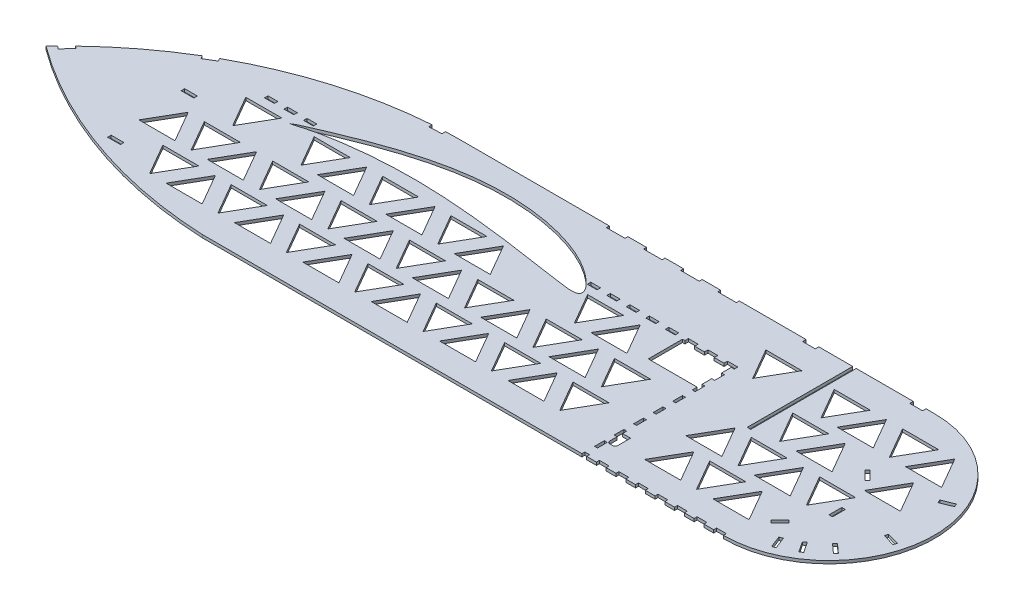
SolidWorks part; units mm, degrees
ref_plane "Front Plane" through (0, 0, 0) normal (0, 0, 1) x (1, 0, 0)
ref_plane "Top Plane" through (0, 0, 0) normal (0, 1, 0) x (1, 0, 0)
ref_plane "Right Plane" through (0, 0, 0) normal (1, 0, 0) x (0, 0, -1)
sketch "Sketch1" plane through (0, 0, 0) normal (0, 1, 0) x (1, 0, 0)
  line L0 (800, 108) -> (0, 108) construction
  line L1 (266.4083, 0) -> (800, 0)
  line L2 (0, 0) -> (0, 216) construction
  line L3 (316.2946, 216) -> (800, 216)
  arc A0 (800, 216) -> (800, 0) centre (800, 108) cw
  arc A2 (266.4083, 0) -> (19.4291, 86.8932) centre (286.1808, 450.645) cw
  arc A4 (19.4291, 86.8932) -> (316.2946, 216) centre (316.2946, -189.8565) cw
  dimension "D1" = 800
  dimension "D2" = 216
extrude "Boss-Extrude1" add sketch "Sketch1" along normal blind 3
sketch "Sketch2" plane through (0, 0, 0) normal (0, -1, 0) x (1, 0, 0)
  line L0 (605.07, -153) -> (605.07, 81) construction
  line L1 (647.57, -153) -> (637.57, -153)
  line L2 (655.07, -153) -> (655.07, -143)
  line L3 (655.07, -118) -> (605.07, -118)
  line L4 (823.6893, -121.2328) -> (814.4969, -130.4252)
  line L5 (814.4969, -130.4252) -> (817.0425, -132.9707)
  line L6 (817.0425, -132.9707) -> (826.2349, -123.7784)
  line L7 (826.2349, -123.7784) -> (823.6893, -121.2328)
  line L8 (823.6893, -121.2328) -> (814.4969, -130.4252)
  line L9 (814.4969, -130.4252) -> (817.0425, -132.9707)
  line L10 (817.0425, -132.9707) -> (826.2349, -123.7784)
  line L11 (826.2349, -123.7784) -> (823.6893, -121.2328)
  line L12 (605.07, -153) -> (605.07, -118)
  line L13 (778.5, -216) -> (791.5, -216) construction
  line L14 (791.5, -216) -> (791.5, -212.4) construction
  line L15 (791.5, -212.4) -> (778.5, -212.4) construction
  line L16 (778.5, -212.4) -> (778.5, -216) construction
  line L17 (668.6076, -216) -> (681.6076, -216) construction
  line L18 (681.6076, -216) -> (681.6076, -212.4) construction
  line L19 (681.6076, -212.4) -> (668.6076, -212.4) construction
  line L20 (833.2163, -28.1278) -> (837.9573, -16.0231)
  line L21 (837.9573, -16.0231) -> (834.6052, -14.7102)
  line L22 (834.6052, -14.7102) -> (829.8642, -26.8149)
  line L23 (829.8642, -26.8149) -> (833.2163, -28.1278)
  line L24 (833.2163, -28.1278) -> (837.9573, -16.0231)
  line L25 (837.9573, -16.0231) -> (834.6052, -14.7102)
  line L26 (834.6052, -14.7102) -> (829.8642, -26.8149)
  line L27 (829.8642, -26.8149) -> (833.2163, -28.1278)
  line L28 (839.4566, -85.3169) -> (839.4566, -72.3169)
  line L29 (839.4566, -72.3169) -> (835.8566, -72.3169)
  line L30 (835.8566, -72.3169) -> (835.8566, -85.3169)
  line L31 (835.8566, -85.3169) -> (839.4566, -85.3169)
  line L32 (839.4566, -85.3169) -> (839.4566, -72.3169)
  line L33 (839.4566, -72.3169) -> (835.8566, -72.3169)
  line L34 (835.8566, -72.3169) -> (835.8566, -85.3169)
  line L35 (835.8566, -85.3169) -> (839.4566, -85.3169)
  line L36 (668.6076, -212.4) -> (668.6076, -216) construction
  line L39 (600.2018, -213) -> (581.2018, -213) construction
  line L40 (658.07, -25.4734) -> (658.07, -38.6734)
  line L41 (663.77, -22.9734) -> (660.57, -22.9734)
  line L42 (666.27, -38.6734) -> (666.27, -25.4734)
  line L43 (658.07, -38.6734) -> (666.27, -38.6734)
  line L44 (658.07, -25.4734) -> (658.07, -33)
  line L45 (663.77, -22.9734) -> (660.57, -22.9734)
  line L46 (666.27, -38.6734) -> (666.27, -25.4734)
  line L47 (658.07, -38.6734) -> (666.27, -38.6734)
  line L48 (581.2018, -213) -> (581.2018, -216) construction
  line L49 (581.2018, -216) -> (600.2018, -216) construction
  line L50 (600.2018, -216) -> (600.2018, -213) construction
  line L51 (562.2018, -213) -> (543.2018, -213) construction
  line L52 (543.2018, -213) -> (543.2018, -216) construction
  line L53 (543.2018, -216) -> (562.2018, -216) construction
  line L54 (562.2018, -216) -> (562.2018, -213) construction
  line L55 (524.2018, -213) -> (505.2018, -213) construction
  line L56 (505.2018, -213) -> (505.2018, -216) construction
  line L57 (505.2018, -216) -> (524.2018, -216) construction
  line L58 (524.2018, -216) -> (524.2018, -213) construction
  line L59 (486.2018, -213) -> (467.2018, -213) construction
  line L60 (467.2018, -213) -> (467.2018, -216) construction
  line L61 (467.2018, -216) -> (486.2018, -216) construction
  line L62 (486.2018, -216) -> (486.2018, -213) construction
  line L63 (286.6536, -215.0679) -> (299.64, -215.6627) construction
  line L64 (299.64, -215.6627) -> (299.8047, -212.0664) construction
  line L65 (299.8047, -212.0664) -> (286.8183, -211.4717) construction
  line L66 (286.8183, -211.4717) -> (286.6536, -215.0679) construction
  line L67 (107.8918, -158.4076) -> (119.0512, -165.0761) construction
  line L68 (119.0512, -165.0761) -> (120.8979, -161.9858) construction
  line L69 (120.8979, -161.9858) -> (109.7385, -155.3173) construction
  line L70 (109.7385, -155.3173) -> (107.8918, -158.4076) construction
  line L71 (25.2251, -93.1105) -> (34.0897, -102.6194) construction
  line L72 (34.0897, -102.6194) -> (36.7229, -100.1646) construction
  line L73 (36.7229, -100.1646) -> (27.8584, -90.6557) construction
  line L74 (27.8584, -90.6557) -> (25.2251, -93.1105) construction
  line L76 (141.0425, -116.6591) -> (128.0425, -116.6591) construction
  line L77 (128.0425, -116.6591) -> (128.0425, -120.2591) construction
  line L79 (212.57, -142.8618) -> (212.57, -142.8948)
  line L80 (128.0425, -120.2591) -> (141.0425, -120.2591) construction
  line L81 (141.0425, -120.2591) -> (141.0425, -116.6591) construction
  line L82 (144.694, -37.8042) -> (131.694, -37.8042) construction
  line L83 (131.694, -37.8042) -> (131.694, -41.4042) construction
  line L84 (131.694, -41.4042) -> (144.694, -41.4042) construction
  line L85 (144.694, -41.4042) -> (144.694, -37.8042) construction
  line L99 (141.0425, -116.6591) -> (128.0425, -116.6591)
  line L101 (128.0425, -116.6591) -> (128.0425, -120.2591)
  line L102 (128.0425, -120.2591) -> (141.0425, -120.2591)
  line L104 (141.0425, -120.2591) -> (141.0425, -116.6591)
  line L105 (144.694, -37.8042) -> (131.694, -37.8042)
  line L106 (131.694, -37.8042) -> (131.694, -41.4042)
  line L108 (131.694, -41.4042) -> (144.694, -41.4042)
  line L110 (144.694, -41.4042) -> (144.694, -37.8042)
  line L111 (237.2859, -101.1604) -> (274.2268, -101.1604)
  line L131 (537.57, -153) -> (527.57, -153) construction
  line L132 (527.57, -153) -> (527.57, -156.6) construction
  line L133 (527.57, -156.6) -> (537.57, -156.6) construction
  line L134 (537.57, -156.6) -> (537.57, -153) construction
  line L135 (557.57, -153) -> (547.57, -153) construction
  line L136 (547.57, -153) -> (547.57, -156.6) construction
  line L137 (547.57, -156.6) -> (557.57, -156.6) construction
  line L138 (557.57, -156.6) -> (557.57, -153) construction
  line L139 (577.57, -153) -> (567.57, -153) construction
  line L140 (567.57, -153) -> (567.57, -156.6) construction
  line L141 (567.57, -156.6) -> (577.57, -156.6) construction
  line L142 (577.57, -156.6) -> (577.57, -153) construction
  line L143 (597.57, -153) -> (587.57, -153) construction
  line L144 (587.57, -153) -> (587.57, -156.6) construction
  line L145 (587.57, -156.6) -> (597.57, -156.6) construction
  line L146 (597.57, -156.6) -> (597.57, -153) construction
  line L148 (607.57, -153) -> (607.57, -156.6) construction
  line L149 (607.57, -156.6) -> (617.57, -156.6) construction
  line L150 (617.57, -156.6) -> (617.57, -153) construction
  line L152 (627.57, -153) -> (627.57, -156.6) construction
  line L153 (627.57, -156.6) -> (637.57, -156.6) construction
  line L154 (637.57, -156.6) -> (637.57, -153) construction
  line L155 (658.07, -153) -> (647.57, -153) construction
  line L156 (647.57, -153) -> (647.57, -156.6) construction
  line L157 (647.57, -156.6) -> (658.07, -156.6) construction
  line L158 (658.07, -156.6) -> (658.07, -153) construction
  line L160 (655.07, -143) -> (658.07, -143) construction
  line L161 (658.07, -143) -> (658.07, -133) construction
  line L162 (658.07, -133) -> (655.07, -133) construction
  line L163 (655.07, -113) -> (655.07, -123) construction
  line L164 (655.07, -123) -> (658.07, -123) construction
  line L165 (658.07, -123) -> (658.07, -113) construction
  line L166 (658.07, -113) -> (655.07, -113) construction
  line L167 (655.07, -93) -> (655.07, -103) construction
  line L168 (655.07, -103) -> (658.07, -103) construction
  line L169 (658.07, -103) -> (658.07, -93) construction
  line L170 (658.07, -93) -> (655.07, -93) construction
  line L171 (655.07, -73) -> (655.07, -83) construction
  line L172 (655.07, -83) -> (658.07, -83) construction
  line L173 (658.07, -83) -> (658.07, -73) construction
  line L174 (658.07, -73) -> (655.07, -73) construction
  line L175 (655.07, -53) -> (655.07, -63) construction
  line L176 (655.07, -63) -> (658.07, -63) construction
  line L177 (658.07, -63) -> (658.07, -53) construction
  line L178 (658.07, -53) -> (655.07, -53) construction
  line L179 (655.07, -33) -> (655.07, -43) construction
  line L180 (655.07, -43) -> (658.07, -43) construction
  line L182 (658.07, -33) -> (655.07, -33) construction
  line L183 (655.07, -13) -> (655.07, -23) construction
  line L184 (655.07, -23) -> (658.07, -23) construction
  line L185 (658.07, -23) -> (658.07, -13) construction
  line L186 (658.07, -13) -> (655.07, -13) construction
  line L187 (660, 0) -> (655.07, 0) construction
  line L188 (879.4661, -142.1765) -> (891.5128, -147.063) construction
  line L189 (891.5128, -147.063) -> (892.866, -143.727) construction
  line L190 (892.866, -143.727) -> (880.8193, -138.8405) construction
  line L191 (880.8193, -138.8405) -> (879.4661, -142.1765) construction
  line L192 (883.5641, -85.6407) -> (896.0497, -82.0199) construction
  line L193 (896.0497, -82.0199) -> (895.047, -78.5624) construction
  line L194 (895.047, -78.5624) -> (882.5614, -82.1832) construction
  line L195 (882.5614, -82.1832) -> (883.5641, -85.6407) construction
  line L196 (865.4007, -51.3816) -> (875.0501, -42.6702) construction
  line L197 (875.0501, -42.6702) -> (872.6378, -39.9981) construction
  line L198 (872.6378, -39.9981) -> (862.9883, -48.7095) construction
  line L199 (862.9883, -48.7095) -> (865.4007, -51.3816) construction
  line L200 (849.1147, -36.7915) -> (856.2715, -25.9389) construction
  line L201 (856.2715, -25.9389) -> (853.2661, -23.957) construction
  line L202 (853.2661, -23.957) -> (846.1093, -34.8096) construction
  line L203 (846.1093, -34.8096) -> (849.1147, -36.7915) construction
  line L204 (822.4089, -44.7346) -> (813.2165, -35.5422) construction
  line L205 (813.2165, -35.5422) -> (810.6709, -38.0878) construction
  line L206 (810.6709, -38.0878) -> (819.8633, -47.2801) construction
  line L207 (819.8633, -47.2801) -> (822.4089, -44.7346) construction
  line L208 (879.4661, -142.1765) -> (891.5128, -147.063)
  line L209 (891.5128, -147.063) -> (892.866, -143.727)
  line L210 (892.866, -143.727) -> (880.8193, -138.8405)
  line L211 (880.8193, -138.8405) -> (879.4661, -142.1765)
  line L212 (883.5641, -85.6407) -> (896.0497, -82.0199)
  line L213 (896.0497, -82.0199) -> (895.047, -78.5624)
  line L214 (895.047, -78.5624) -> (882.5614, -82.1832)
  line L215 (882.5614, -82.1832) -> (883.5641, -85.6407)
  line L216 (865.4007, -51.3816) -> (875.0501, -42.6702)
  line L217 (875.0501, -42.6702) -> (872.6378, -39.9981)
  line L218 (872.6378, -39.9981) -> (862.9883, -48.7095)
  line L219 (862.9883, -48.7095) -> (865.4007, -51.3816)
  line L220 (849.1147, -36.7915) -> (856.2715, -25.9389)
  line L221 (856.2715, -25.9389) -> (853.2661, -23.957)
  line L222 (853.2661, -23.957) -> (846.1093, -34.8096)
  line L223 (846.1093, -34.8096) -> (849.1147, -36.7915)
  line L224 (822.4089, -44.7346) -> (813.2165, -35.5422)
  line L225 (813.2165, -35.5422) -> (810.6709, -38.0878)
  line L226 (810.6709, -38.0878) -> (819.8633, -47.2801)
  line L227 (819.8633, -47.2801) -> (822.4089, -44.7346)
  line L228 (655.07, 0) -> (655.07, -3) construction
  line L229 (655.07, -3) -> (660, -3) construction
  line L230 (660, -3) -> (660, 0) construction
  line L231 (680, 0) -> (670, 0) construction
  line L232 (670, 0) -> (670, -3) construction
  line L233 (670, -3) -> (680, -3) construction
  line L234 (680, -3) -> (680, 0) construction
  line L235 (700, 0) -> (690, 0) construction
  line L236 (690, 0) -> (690, -3) construction
  line L237 (690, -3) -> (700, -3) construction
  line L238 (700, -3) -> (700, 0) construction
  line L239 (720, 0) -> (710, 0) construction
  line L240 (710, 0) -> (710, -3) construction
  line L241 (710, -3) -> (720, -3) construction
  line L242 (720, -3) -> (720, 0) construction
  line L243 (740, 0) -> (730, 0) construction
  line L244 (730, 0) -> (730, -3) construction
  line L245 (730, -3) -> (740, -3) construction
  line L246 (740, -3) -> (740, 0) construction
  line L247 (760, 0) -> (750, 0) construction
  line L248 (750, 0) -> (750, -3) construction
  line L249 (750, -3) -> (760, -3) construction
  line L250 (760, -3) -> (760, 0) construction
  line L251 (780, 0) -> (770, 0) construction
  line L252 (770, 0) -> (770, -3) construction
  line L253 (770, -3) -> (780, -3) construction
  line L254 (780, -3) -> (780, 0) construction
  line L255 (800, 0) -> (790, 0) construction
  line L256 (790, 0) -> (790, -3) construction
  line L257 (790, -3) -> (800, -3) construction
  line L258 (800, -3) -> (800, 0) construction
  line L259 (778.5, -216) -> (791.5, -216)
  line L260 (791.5, -216) -> (791.5, -212.4)
  line L261 (791.5, -212.4) -> (778.5, -212.4)
  line L262 (778.5, -212.4) -> (778.5, -216)
  line L263 (668.6076, -216) -> (681.6076, -216)
  line L264 (681.6076, -216) -> (681.6076, -212.4)
  line L265 (681.6076, -212.4) -> (668.6076, -212.4)
  line L266 (668.6076, -212.4) -> (668.6076, -216)
  line L267 (600.2018, -213) -> (581.2018, -213)
  line L268 (581.2018, -213) -> (581.2018, -216)
  line L269 (581.2018, -216) -> (600.2018, -216)
  line L270 (600.2018, -216) -> (600.2018, -213)
  line L271 (562.2018, -213) -> (543.2018, -213)
  line L272 (543.2018, -213) -> (543.2018, -216)
  line L273 (543.2018, -216) -> (562.2018, -216)
  line L274 (562.2018, -216) -> (562.2018, -213)
  line L275 (524.2018, -213) -> (505.2018, -213)
  line L276 (505.2018, -213) -> (505.2018, -216)
  line L277 (505.2018, -216) -> (524.2018, -216)
  line L278 (524.2018, -216) -> (524.2018, -213)
  line L279 (486.2018, -213) -> (467.2018, -213)
  line L280 (467.2018, -213) -> (467.2018, -216)
  line L281 (467.2018, -216) -> (486.2018, -216)
  line L282 (486.2018, -216) -> (486.2018, -213)
  line L283 (286.6536, -215.0679) -> (299.64, -215.6627)
  line L284 (299.64, -215.6627) -> (299.8047, -212.0664)
  line L285 (299.8047, -212.0664) -> (286.8183, -211.4717)
  line L286 (286.8183, -211.4717) -> (286.6536, -215.0679)
  line L287 (107.8918, -158.4076) -> (119.0512, -165.0761)
  line L288 (119.0512, -165.0761) -> (120.8979, -161.9858)
  line L289 (120.8979, -161.9858) -> (109.7385, -155.3173)
  line L290 (109.7385, -155.3173) -> (107.8918, -158.4076)
  line L291 (25.2251, -93.1105) -> (34.0897, -102.6194)
  line L292 (34.0897, -102.6194) -> (36.7229, -100.1646)
  line L293 (36.7229, -100.1646) -> (27.8584, -90.6557)
  line L294 (27.8584, -90.6557) -> (25.2251, -93.1105)
  line L351 (537.57, -153) -> (527.57, -153)
  line L352 (527.57, -153) -> (527.57, -156.6)
  line L353 (527.57, -156.6) -> (537.57, -156.6)
  line L354 (537.57, -156.6) -> (537.57, -153)
  line L355 (557.57, -153) -> (547.57, -153)
  line L356 (547.57, -153) -> (547.57, -156.6)
  line L357 (547.57, -156.6) -> (557.57, -156.6)
  line L358 (557.57, -156.6) -> (557.57, -153)
  line L359 (577.57, -153) -> (567.57, -153)
  line L360 (567.57, -153) -> (567.57, -156.6)
  line L361 (567.57, -156.6) -> (577.57, -156.6)
  line L362 (577.57, -156.6) -> (577.57, -153)
  line L363 (597.57, -153) -> (587.57, -153)
  line L364 (587.57, -153) -> (587.57, -156.6)
  line L365 (587.57, -156.6) -> (597.57, -156.6)
  line L366 (597.57, -156.6) -> (597.57, -153)
  line L368 (607.57, -153) -> (607.57, -156.6)
  line L369 (607.57, -156.6) -> (617.57, -156.6)
  line L370 (617.57, -156.6) -> (617.57, -153)
  line L372 (627.57, -153) -> (627.57, -156.6)
  line L373 (627.57, -156.6) -> (637.57, -156.6)
  line L374 (637.57, -156.6) -> (637.57, -153)
  line L375 (658.07, -153) -> (655.07, -153)
  line L376 (647.57, -153) -> (647.57, -156.6)
  line L377 (647.57, -156.6) -> (658.07, -156.6)
  line L378 (658.07, -156.6) -> (658.07, -153)
  line L380 (655.07, -143) -> (658.07, -143)
  line L381 (658.07, -143) -> (658.07, -133)
  line L382 (658.07, -133) -> (655.07, -133)
  line L383 (655.07, -113) -> (655.07, -118)
  line L384 (655.07, -123) -> (658.07, -123)
  line L385 (658.07, -123) -> (658.07, -113)
  line L386 (658.07, -113) -> (655.07, -113)
  line L387 (655.07, -93) -> (655.07, -103)
  line L388 (655.07, -103) -> (658.07, -103)
  line L389 (658.07, -103) -> (658.07, -93)
  line L390 (658.07, -93) -> (655.07, -93)
  line L391 (655.07, -73) -> (655.07, -83)
  line L392 (655.07, -83) -> (658.07, -83)
  line L393 (658.07, -83) -> (658.07, -73)
  line L394 (658.07, -73) -> (655.07, -73)
  line L395 (655.07, -53) -> (655.07, -63)
  line L396 (655.07, -63) -> (658.07, -63)
  line L397 (658.07, -63) -> (658.07, -53)
  line L398 (658.07, -53) -> (655.07, -53)
  line L399 (655.07, -33) -> (655.07, -43)
  line L400 (655.07, -43) -> (658.07, -43)
  line L401 (658.07, -43) -> (658.07, -38.6734)
  line L402 (658.07, -33) -> (655.07, -33)
  line L403 (655.07, -13) -> (655.07, -23)
  line L404 (655.07, -23) -> (658.07, -23)
  line L405 (658.07, -23) -> (658.07, -13)
  line L406 (658.07, -13) -> (655.07, -13)
  line L407 (660, 0) -> (655.07, 0)
  line L408 (655.07, 0) -> (655.07, -3)
  line L409 (655.07, -3) -> (660, -3)
  line L410 (660, -3) -> (660, 0)
  line L411 (680, 0) -> (670, 0)
  line L412 (670, 0) -> (670, -3)
  line L413 (670, -3) -> (680, -3)
  line L414 (680, -3) -> (680, 0)
  line L415 (700, 0) -> (690, 0)
  line L416 (690, 0) -> (690, -3)
  line L417 (690, -3) -> (700, -3)
  line L418 (700, -3) -> (700, 0)
  line L419 (720, 0) -> (710, 0)
  line L420 (710, 0) -> (710, -3)
  line L421 (710, -3) -> (720, -3)
  line L422 (720, -3) -> (720, 0)
  line L423 (740, 0) -> (730, 0)
  line L424 (730, 0) -> (730, -3)
  line L425 (730, -3) -> (740, -3)
  line L426 (740, -3) -> (740, 0)
  line L427 (760, 0) -> (750, 0)
  line L428 (750, 0) -> (750, -3)
  line L429 (750, -3) -> (760, -3)
  line L430 (760, -3) -> (760, 0)
  line L431 (780, 0) -> (770, 0)
  line L432 (770, 0) -> (770, -3)
  line L433 (770, -3) -> (780, -3)
  line L434 (780, -3) -> (780, 0)
  line L435 (800, 0) -> (790, 0)
  line L436 (790, 0) -> (790, -3)
  line L437 (790, -3) -> (800, -3)
  line L438 (800, -3) -> (800, 0)
  line L439 (655.07, -133) -> (655.07, -123)
  line L440 (627.57, -153) -> (617.57, -153)
  line L441 (607.57, -153) -> (605.07, -153)
  line L443 (274.2268, -101.1604) -> (255.7563, -69.1686)
  line L444 (255.7563, -69.1686) -> (237.2859, -101.1604)
  line L445 (202.2859, -69.1686) -> (239.2268, -69.1686)
  line L449 (239.2268, -69.1686) -> (220.7563, -101.1604)
  line L450 (220.7563, -101.1604) -> (202.2859, -69.1686)
  line L451 (220.7563, -101.1604) -> (202.2859, -69.1686) construction
  line L452 (239.2268, -69.1686) -> (220.7563, -101.1604) construction
  line L453 (202.2859, -69.1686) -> (239.2268, -69.1686) construction
  line L462 (187.07, -153) -> (177.07, -153) construction
  line L463 (177.07, -153) -> (177.07, -156.6) construction
  line L464 (177.07, -156.6) -> (187.07, -156.6) construction
  line L465 (187.07, -156.6) -> (187.07, -153) construction
  line L466 (207.07, -153) -> (197.07, -153) construction
  line L467 (197.07, -153) -> (197.07, -156.6) construction
  line L468 (197.07, -156.6) -> (207.07, -156.6) construction
  line L469 (207.07, -156.6) -> (207.07, -153) construction
  line L470 (227.07, -153) -> (217.07, -153) construction
  line L471 (217.07, -153) -> (217.07, -156.6) construction
  line L472 (217.07, -156.6) -> (227.07, -156.6) construction
  line L473 (227.07, -156.6) -> (227.07, -153) construction
  line L474 (517.57, -153) -> (507.57, -153) construction
  line L475 (507.57, -153) -> (507.57, -156.6) construction
  line L476 (507.57, -156.6) -> (517.57, -156.6) construction
  line L477 (517.57, -156.6) -> (517.57, -153) construction
  line L478 (187.07, -153) -> (177.07, -153)
  line L479 (177.07, -153) -> (177.07, -156.6)
  line L480 (177.07, -156.6) -> (187.07, -156.6)
  line L481 (187.07, -156.6) -> (187.07, -153)
  line L482 (207.07, -153) -> (197.07, -153)
  line L483 (197.07, -153) -> (197.07, -156.6)
  line L484 (197.07, -156.6) -> (207.07, -156.6)
  line L485 (207.07, -156.6) -> (207.07, -153)
  line L486 (227.07, -153) -> (217.07, -153)
  line L487 (217.07, -153) -> (217.07, -156.6)
  line L488 (217.07, -156.6) -> (227.07, -156.6)
  line L489 (227.07, -156.6) -> (227.07, -153)
  line L490 (517.57, -153) -> (507.57, -153)
  line L491 (507.57, -153) -> (507.57, -156.6)
  line L492 (507.57, -156.6) -> (517.57, -156.6)
  line L493 (517.57, -156.6) -> (517.57, -153)
  line L504 (202.2859, -26.9901) -> (239.2268, -26.9901)
  line L514 (239.2268, -26.9901) -> (220.7563, -58.9818)
  line L515 (132.2859, -69.1686) -> (169.2268, -69.1686)
  line L516 (150.7563, -101.1604) -> (132.2859, -69.1686)
  line L517 (169.2268, -69.1686) -> (150.7563, -101.1604)
  line L518 (202.2859, -69.1686) -> (132.2859, -69.1686) construction
  line L519 (150.7563, -101.1604) -> (220.7563, -101.1604) construction
  line L520 (221.2596, -58.9818) -> (202.7892, -26.9901) construction
  line L521 (167.2859, -101.1604) -> (204.2268, -101.1604)
  line L522 (185.7563, -69.1686) -> (167.2859, -101.1604)
  line L523 (204.2268, -101.1604) -> (185.7563, -69.1686)
  line L524 (239.73, -26.9901) -> (221.2596, -58.9818) construction
  line L525 (202.7892, -26.9901) -> (239.73, -26.9901) construction
  line L526 (132.2859, -26.9901) -> (169.2268, -26.9901) construction
  line L527 (150.7563, -58.9818) -> (132.2859, -26.9901) construction
  line L528 (169.2268, -26.9901) -> (150.7563, -58.9818) construction
  line L529 (166.9552, -58.9818) -> (203.896, -58.9818)
  line L530 (185.4256, -26.9901) -> (166.9552, -58.9818)
  line L531 (203.896, -58.9818) -> (185.4256, -26.9901)
  line L532 (220.7563, -58.9818) -> (202.2859, -26.9901)
  line L533 (236.9552, -58.9818) -> (273.896, -58.9818)
  line L534 (716.4, -108) -> (716.4, -216)
  line L535 (716.4, -216) -> (720, -216)
  line L536 (720, -216) -> (720, -108)
  line L537 (720, -108) -> (716.4, -108)
  line L538 (716.4, -108) -> (716.4, -216)
  line L539 (716.4, -216) -> (720, -216)
  line L540 (720, -216) -> (720, -108)
  line L541 (720, -108) -> (716.4, -108)
  line L542 (273.896, -58.9818) -> (255.4256, -26.9901)
  line L543 (255.4256, -26.9901) -> (236.9552, -58.9818)
  line L544 (307.2859, -101.1604) -> (344.2268, -101.1604)
  line L545 (344.2268, -101.1604) -> (325.7563, -69.1686)
  line L546 (325.7563, -69.1686) -> (307.2859, -101.1604)
  line L547 (272.2859, -69.1686) -> (309.2268, -69.1686)
  line L548 (309.2268, -69.1686) -> (290.7563, -101.1604)
  line L549 (290.7563, -101.1604) -> (272.2859, -69.1686)
  line L550 (272.2859, -26.9901) -> (309.2268, -26.9901)
  line L551 (309.2268, -26.9901) -> (290.7563, -58.9818)
  line L552 (290.7563, -58.9818) -> (272.2859, -26.9901)
  line L553 (306.9552, -58.9818) -> (343.896, -58.9818)
  line L554 (343.896, -58.9818) -> (325.4256, -26.9901)
  line L555 (325.4256, -26.9901) -> (306.9552, -58.9818)
  line L556 (377.2859, -101.1604) -> (414.2268, -101.1604)
  line L557 (414.2268, -101.1604) -> (395.7563, -69.1686)
  line L558 (395.7563, -69.1686) -> (377.2859, -101.1604)
  line L559 (342.2859, -69.1686) -> (379.2268, -69.1686)
  line L560 (379.2268, -69.1686) -> (360.7563, -101.1604)
  line L561 (360.7563, -101.1604) -> (342.2859, -69.1686)
  line L562 (342.2859, -26.9901) -> (379.2268, -26.9901)
  line L563 (379.2268, -26.9901) -> (360.7563, -58.9818)
  line L564 (360.7563, -58.9818) -> (342.2859, -26.9901)
  line L565 (376.9552, -58.9818) -> (413.896, -58.9818)
  line L566 (413.896, -58.9818) -> (395.4256, -26.9901)
  line L567 (395.4256, -26.9901) -> (376.9552, -58.9818)
  line L568 (447.2859, -101.1604) -> (484.2268, -101.1604)
  line L569 (484.2268, -101.1604) -> (465.7563, -69.1686)
  line L570 (465.7563, -69.1686) -> (447.2859, -101.1604)
  line L571 (412.2859, -69.1686) -> (449.2268, -69.1686)
  line L572 (449.2268, -69.1686) -> (430.7563, -101.1604)
  line L573 (430.7563, -101.1604) -> (412.2859, -69.1686)
  line L574 (412.2859, -26.9901) -> (449.2268, -26.9901)
  line L575 (449.2268, -26.9901) -> (430.7563, -58.9818)
  line L576 (430.7563, -58.9818) -> (412.2859, -26.9901)
  line L577 (446.9552, -58.9818) -> (483.896, -58.9818)
  line L578 (483.896, -58.9818) -> (465.4256, -26.9901)
  line L579 (465.4256, -26.9901) -> (446.9552, -58.9818)
  line L580 (517.2859, -101.1604) -> (554.2268, -101.1604)
  line L581 (554.2268, -101.1604) -> (535.7563, -69.1686)
  line L582 (535.7563, -69.1686) -> (517.2859, -101.1604)
  line L583 (482.2859, -69.1686) -> (519.2268, -69.1686)
  line L584 (519.2268, -69.1686) -> (500.7563, -101.1604)
  line L585 (500.7563, -101.1604) -> (482.2859, -69.1686)
  line L586 (482.2859, -26.9901) -> (519.2268, -26.9901)
  line L587 (519.2268, -26.9901) -> (500.7563, -58.9818)
  line L588 (500.7563, -58.9818) -> (482.2859, -26.9901)
  line L589 (516.9552, -58.9818) -> (553.896, -58.9818)
  line L590 (553.896, -58.9818) -> (535.4256, -26.9901)
  line L591 (535.4256, -26.9901) -> (516.9552, -58.9818)
  line L592 (587.2859, -101.1604) -> (624.2268, -101.1604)
  line L593 (624.2268, -101.1604) -> (605.7563, -69.1686)
  line L594 (605.7563, -69.1686) -> (587.2859, -101.1604)
  line L595 (552.2859, -69.1686) -> (589.2268, -69.1686)
  line L596 (589.2268, -69.1686) -> (570.7563, -101.1604)
  line L597 (570.7563, -101.1604) -> (552.2859, -69.1686)
  line L598 (552.2859, -26.9901) -> (589.2268, -26.9901)
  line L599 (589.2268, -26.9901) -> (570.7563, -58.9818)
  line L600 (570.7563, -58.9818) -> (552.2859, -26.9901)
  line L601 (586.9552, -58.9818) -> (623.896, -58.9818)
  line L602 (623.896, -58.9818) -> (605.4256, -26.9901)
  line L603 (605.4256, -26.9901) -> (586.9552, -58.9818)
  line L616 (727.2859, -101.1604) -> (764.2268, -101.1604)
  line L617 (764.2268, -101.1604) -> (745.7563, -69.1686)
  line L618 (745.7563, -69.1686) -> (727.2859, -101.1604)
  line L619 (692.2859, -69.1686) -> (729.2268, -69.1686)
  line L620 (729.2268, -69.1686) -> (710.7563, -101.1604)
  line L621 (710.7563, -101.1604) -> (692.2859, -69.1686)
  line L622 (692.2859, -26.9901) -> (729.2268, -26.9901)
  line L623 (729.2268, -26.9901) -> (710.7563, -58.9818)
  line L624 (710.7563, -58.9818) -> (692.2859, -26.9901)
  line L625 (726.9552, -58.9818) -> (763.896, -58.9818)
  line L626 (763.896, -58.9818) -> (745.4256, -26.9901)
  line L627 (745.4256, -26.9901) -> (726.9552, -58.9818)
  line L628 (797.2859, -101.1604) -> (834.2268, -101.1604)
  line L629 (834.2268, -101.1604) -> (815.7563, -69.1686)
  line L630 (815.7563, -69.1686) -> (797.2859, -101.1604)
  line L631 (762.2859, -69.1686) -> (799.2268, -69.1686)
  line L632 (799.2268, -69.1686) -> (780.7563, -101.1604)
  line L633 (780.7563, -101.1604) -> (762.2859, -69.1686)
  line L634 (762.2859, -26.9901) -> (799.2268, -26.9901)
  line L635 (799.2268, -26.9901) -> (780.7563, -58.9818)
  line L636 (780.7563, -58.9818) -> (762.2859, -26.9901)
  line L661 (236.9552, -143.9818) -> (273.896, -143.9818)
  line L662 (273.896, -143.9818) -> (255.4256, -111.9901)
  line L663 (255.4256, -111.9901) -> (236.9552, -143.9818)
  line L670 (272.2859, -111.9901) -> (309.2268, -111.9901)
  line L671 (309.2268, -111.9901) -> (290.7563, -143.9818)
  line L672 (290.7563, -143.9818) -> (272.2859, -111.9901)
  line L673 (306.9552, -143.9818) -> (343.896, -143.9818)
  line L674 (343.896, -143.9818) -> (325.4256, -111.9901)
  line L675 (325.4256, -111.9901) -> (306.9552, -143.9818)
  line L682 (342.2859, -111.9901) -> (379.2268, -111.9901)
  line L683 (379.2268, -111.9901) -> (360.7563, -143.9818)
  line L684 (360.7563, -143.9818) -> (342.2859, -111.9901)
  line L685 (376.9552, -143.9818) -> (413.896, -143.9818)
  line L686 (413.896, -143.9818) -> (395.4256, -111.9901)
  line L687 (395.4256, -111.9901) -> (376.9552, -143.9818)
  line L694 (412.2859, -111.9901) -> (449.2268, -111.9901)
  line L695 (449.2268, -111.9901) -> (430.7563, -143.9818)
  line L696 (430.7563, -143.9818) -> (412.2859, -111.9901)
  line L709 (516.9552, -143.9818) -> (553.896, -143.9818)
  line L710 (553.896, -143.9818) -> (535.4256, -111.9901)
  line L711 (535.4256, -111.9901) -> (516.9552, -143.9818)
  line L718 (552.2859, -111.9901) -> (589.2268, -111.9901)
  line L719 (589.2268, -111.9901) -> (570.7563, -143.9818)
  line L720 (570.7563, -143.9818) -> (552.2859, -111.9901)
  line L724 (657.2859, -186.1604) -> (694.2268, -186.1604)
  line L725 (694.2268, -186.1604) -> (675.7563, -154.1686)
  line L726 (675.7563, -154.1686) -> (657.2859, -186.1604)
  line L736 (727.2859, -186.1604) -> (764.2268, -186.1604)
  line L737 (764.2268, -186.1604) -> (745.7563, -154.1686)
  line L738 (745.7563, -154.1686) -> (727.2859, -186.1604)
  line L745 (726.9552, -143.9818) -> (763.896, -143.9818)
  line L746 (763.896, -143.9818) -> (745.4256, -111.9901)
  line L747 (745.4256, -111.9901) -> (726.9552, -143.9818)
  line L748 (797.2859, -186.1604) -> (834.2268, -186.1604)
  line L749 (834.2268, -186.1604) -> (815.7563, -154.1686)
  line L750 (815.7563, -154.1686) -> (797.2859, -186.1604)
  line L751 (762.2859, -154.1686) -> (799.2268, -154.1686)
  line L752 (799.2268, -154.1686) -> (780.7563, -186.1604)
  line L753 (780.7563, -186.1604) -> (762.2859, -154.1686)
  line L754 (762.2859, -111.9901) -> (799.2268, -111.9901)
  line L755 (799.2268, -111.9901) -> (780.7563, -143.9818)
  line L756 (780.7563, -143.9818) -> (762.2859, -111.9901)
  line L763 (832.2859, -154.1686) -> (869.2268, -154.1686)
  line L764 (869.2268, -154.1686) -> (850.7563, -186.1604)
  line L765 (850.7563, -186.1604) -> (832.2859, -154.1686)
  line L766 (832.2859, -111.9901) -> (869.2268, -111.9901)
  line L767 (869.2268, -111.9901) -> (850.7563, -143.9818)
  line L768 (850.7563, -143.9818) -> (832.2859, -111.9901)
  line L901 (166.9552, -143.9818) -> (203.896, -143.9818)
  line L902 (203.896, -143.9818) -> (185.4256, -111.9901)
  line L903 (185.4256, -111.9901) -> (166.9552, -143.9818)
  line L916 (167.2859, -101.1604) -> (237.2859, -101.1604) construction
  line L917 (167.2859, -101.1604) -> (167.2859, -186.1604) construction
  line L918 (832.2859, -69.1686) -> (869.2268, -69.1686) [skipped]
  line L919 (869.2268, -69.1686) -> (850.7563, -101.1604) [skipped]
  line L920 (850.7563, -101.1604) -> (832.2859, -69.1686) [skipped]
  line L921 (796.9552, -58.9818) -> (833.896, -58.9818) [skipped]
  line L922 (833.896, -58.9818) -> (815.4256, -26.9901) [skipped]
  line L923 (815.4256, -26.9901) -> (796.9552, -58.9818) [skipped]
  line L924 (796.9552, -143.9818) -> (833.896, -143.9818) [skipped]
  line L925 (833.896, -143.9818) -> (815.4256, -111.9901) [skipped]
  line L926 (815.4256, -111.9901) -> (796.9552, -143.9818) [skipped]
  line L927 (866.9552, -58.9818) -> (903.896, -58.9818) [skipped]
  line L928 (903.896, -58.9818) -> (885.4256, -26.9901) [skipped]
  line L929 (885.4256, -26.9901) -> (866.9552, -58.9818) [skipped]
  line L930 (832.2859, -26.9901) -> (869.2268, -26.9901) [skipped]
  line L931 (869.2268, -26.9901) -> (850.7563, -58.9818) [skipped]
  line L932 (850.7563, -58.9818) -> (832.2859, -26.9901) [skipped]
  line L933 (867.2859, -101.1604) -> (904.2268, -101.1604) [skipped]
  line L934 (904.2268, -101.1604) -> (885.7563, -69.1686) [skipped]
  line L935 (885.7563, -69.1686) -> (867.2859, -101.1604) [skipped]
  line L936 (866.9552, -143.9818) -> (903.896, -143.9818) [skipped]
  line L937 (903.896, -143.9818) -> (885.4256, -111.9901) [skipped]
  line L938 (885.4256, -111.9901) -> (866.9552, -143.9818) [skipped]
  line L939 (867.2859, -186.1604) -> (904.2268, -186.1604) [skipped]
  line L940 (904.2268, -186.1604) -> (885.7563, -154.1686) [skipped]
  line L941 (885.7563, -154.1686) -> (867.2859, -186.1604) [skipped]
  line L942 (832.2859, -196.9901) -> (869.2268, -196.9901) [skipped]
  line L943 (869.2268, -196.9901) -> (850.7563, -228.9818) [skipped]
  line L944 (850.7563, -228.9818) -> (832.2859, -196.9901) [skipped]
  line L945 (796.9552, -228.9818) -> (833.896, -228.9818) [skipped]
  line L946 (833.896, -228.9818) -> (815.4256, -196.9901) [skipped]
  line L947 (815.4256, -196.9901) -> (796.9552, -228.9818) [skipped]
  line L948 (866.9552, -228.9818) -> (903.896, -228.9818) [skipped]
  line L949 (903.896, -228.9818) -> (885.4256, -196.9901) [skipped]
  line L950 (885.4256, -196.9901) -> (866.9552, -228.9818) [skipped]
  line L951 (867.2859, -271.1604) -> (904.2268, -271.1604) [skipped]
  line L952 (904.2268, -271.1604) -> (885.7563, -239.1686) [skipped]
  line L953 (885.7563, -239.1686) -> (867.2859, -271.1604) [skipped]
  line L954 (832.2859, -239.1686) -> (869.2268, -239.1686) [skipped]
  line L955 (869.2268, -239.1686) -> (850.7563, -271.1604) [skipped]
  line L956 (850.7563, -271.1604) -> (832.2859, -239.1686) [skipped]
  line L957 (797.2859, -271.1604) -> (834.2268, -271.1604) [skipped]
  line L958 (834.2268, -271.1604) -> (815.7563, -239.1686) [skipped]
  line L959 (815.7563, -239.1686) -> (797.2859, -271.1604) [skipped]
  line L960 (762.2859, -239.1686) -> (799.2268, -239.1686) [skipped]
  line L961 (799.2268, -239.1686) -> (780.7563, -271.1604) [skipped]
  line L962 (780.7563, -271.1604) -> (762.2859, -239.1686) [skipped]
  line L963 (727.2859, -271.1604) -> (764.2268, -271.1604) [skipped]
  line L964 (764.2268, -271.1604) -> (745.7563, -239.1686) [skipped]
  line L965 (745.7563, -239.1686) -> (727.2859, -271.1604) [skipped]
  line L966 (692.2859, -239.1686) -> (729.2268, -239.1686) [skipped]
  line L967 (729.2268, -239.1686) -> (710.7563, -271.1604) [skipped]
  line L968 (710.7563, -271.1604) -> (692.2859, -239.1686) [skipped]
  line L969 (657.2859, -271.1604) -> (694.2268, -271.1604) [skipped]
  line L970 (694.2268, -271.1604) -> (675.7563, -239.1686) [skipped]
  line L971 (675.7563, -239.1686) -> (657.2859, -271.1604) [skipped]
  line L972 (622.2859, -239.1686) -> (659.2268, -239.1686) [skipped]
  line L973 (659.2268, -239.1686) -> (640.7563, -271.1604) [skipped]
  line L974 (640.7563, -271.1604) -> (622.2859, -239.1686) [skipped]
  line L975 (587.2859, -271.1604) -> (624.2268, -271.1604) [skipped]
  line L976 (624.2268, -271.1604) -> (605.7563, -239.1686) [skipped]
  line L977 (605.7563, -239.1686) -> (587.2859, -271.1604) [skipped]
  line L978 (552.2859, -239.1686) -> (589.2268, -239.1686) [skipped]
  line L979 (589.2268, -239.1686) -> (570.7563, -271.1604) [skipped]
  line L980 (570.7563, -271.1604) -> (552.2859, -239.1686) [skipped]
  line L981 (517.2859, -271.1604) -> (554.2268, -271.1604) [skipped]
  line L982 (554.2268, -271.1604) -> (535.7563, -239.1686) [skipped]
  line L983 (535.7563, -239.1686) -> (517.2859, -271.1604) [skipped]
  line L984 (482.2859, -239.1686) -> (519.2268, -239.1686) [skipped]
  line L985 (519.2268, -239.1686) -> (500.7563, -271.1604) [skipped]
  line L986 (500.7563, -271.1604) -> (482.2859, -239.1686) [skipped]
  line L987 (447.2859, -271.1604) -> (484.2268, -271.1604) [skipped]
  line L988 (484.2268, -271.1604) -> (465.7563, -239.1686) [skipped]
  line L989 (465.7563, -239.1686) -> (447.2859, -271.1604) [skipped]
  line L990 (762.2859, -196.9901) -> (799.2268, -196.9901) [skipped]
  line L991 (799.2268, -196.9901) -> (780.7563, -228.9818) [skipped]
  line L992 (780.7563, -228.9818) -> (762.2859, -196.9901) [skipped]
  line L993 (726.9552, -228.9818) -> (763.896, -228.9818) [skipped]
  line L994 (763.896, -228.9818) -> (745.4256, -196.9901) [skipped]
  line L995 (745.4256, -196.9901) -> (726.9552, -228.9818) [skipped]
  line L996 (692.2859, -196.9901) -> (729.2268, -196.9901) [skipped]
  line L997 (729.2268, -196.9901) -> (710.7563, -228.9818) [skipped]
  line L998 (710.7563, -228.9818) -> (692.2859, -196.9901) [skipped]
  line L999 (656.9552, -228.9818) -> (693.896, -228.9818) [skipped]
  line L1000 (693.896, -228.9818) -> (675.4256, -196.9901) [skipped]
  line L1001 (675.4256, -196.9901) -> (656.9552, -228.9818) [skipped]
  line L1002 (622.2859, -196.9901) -> (659.2268, -196.9901) [skipped]
  line L1003 (659.2268, -196.9901) -> (640.7563, -228.9818) [skipped]
  line L1004 (640.7563, -228.9818) -> (622.2859, -196.9901) [skipped]
  line L1005 (586.9552, -228.9818) -> (623.896, -228.9818) [skipped]
  line L1006 (623.896, -228.9818) -> (605.4256, -196.9901) [skipped]
  line L1007 (605.4256, -196.9901) -> (586.9552, -228.9818) [skipped]
  line L1008 (552.2859, -196.9901) -> (589.2268, -196.9901) [skipped]
  line L1009 (589.2268, -196.9901) -> (570.7563, -228.9818) [skipped]
  line L1010 (570.7563, -228.9818) -> (552.2859, -196.9901) [skipped]
  line L1011 (516.9552, -228.9818) -> (553.896, -228.9818) [skipped]
  line L1012 (553.896, -228.9818) -> (535.4256, -196.9901) [skipped]
  line L1013 (535.4256, -196.9901) -> (516.9552, -228.9818) [skipped]
  line L1014 (482.2859, -196.9901) -> (519.2268, -196.9901) [skipped]
  line L1015 (519.2268, -196.9901) -> (500.7563, -228.9818) [skipped]
  line L1016 (500.7563, -228.9818) -> (482.2859, -196.9901) [skipped]
  line L1017 (692.2859, -154.1686) -> (729.2268, -154.1686) [skipped]
  line L1018 (729.2268, -154.1686) -> (710.7563, -186.1604) [skipped]
  line L1019 (710.7563, -186.1604) -> (692.2859, -154.1686) [skipped]
  line L1020 (692.2859, -111.9901) -> (729.2268, -111.9901) [skipped]
  line L1021 (729.2268, -111.9901) -> (710.7563, -143.9818) [skipped]
  line L1022 (710.7563, -143.9818) -> (692.2859, -111.9901) [skipped]
  line L1023 (622.2859, -154.1686) -> (659.2268, -154.1686) [skipped]
  line L1024 (659.2268, -154.1686) -> (640.7563, -186.1604) [skipped]
  line L1025 (640.7563, -186.1604) -> (622.2859, -154.1686) [skipped]
  line L1026 (622.2859, -111.9901) -> (659.2268, -111.9901) [skipped]
  line L1027 (640.7563, -143.9818) -> (622.2859, -111.9901) [skipped]
  line L1028 (659.2268, -111.9901) -> (640.7563, -143.9818) [skipped]
  line L1029 (622.2859, -69.1686) -> (659.2268, -69.1686) [skipped]
  line L1030 (640.7563, -101.1604) -> (622.2859, -69.1686) [skipped]
  line L1031 (659.2268, -69.1686) -> (640.7563, -101.1604) [skipped]
  line L1032 (622.2859, -26.9901) -> (659.2268, -26.9901) [skipped]
  line L1033 (640.7563, -58.9818) -> (622.2859, -26.9901) [skipped]
  line L1034 (659.2268, -26.9901) -> (640.7563, -58.9818) [skipped]
  line L1035 (675.4256, -26.9901) -> (656.9552, -58.9818) [skipped]
  line L1036 (693.896, -58.9818) -> (675.4256, -26.9901) [skipped]
  line L1037 (656.9552, -58.9818) -> (693.896, -58.9818) [skipped]
  line L1038 (675.7563, -69.1686) -> (657.2859, -101.1604) [skipped]
  line L1039 (694.2268, -101.1604) -> (675.7563, -69.1686) [skipped]
  line L1040 (657.2859, -101.1604) -> (694.2268, -101.1604) [skipped]
  line L1041 (675.4256, -111.9901) -> (656.9552, -143.9818) [skipped]
  line L1042 (693.896, -143.9818) -> (675.4256, -111.9901) [skipped]
  line L1043 (656.9552, -143.9818) -> (693.896, -143.9818) [skipped]
  line L1044 (605.4256, -111.9901) -> (586.9552, -143.9818) [skipped]
  line L1045 (623.896, -143.9818) -> (605.4256, -111.9901) [skipped]
  line L1046 (586.9552, -143.9818) -> (623.896, -143.9818) [skipped]
  line L1047 (482.2859, -154.1686) -> (519.2268, -154.1686) [skipped]
  line L1048 (519.2268, -154.1686) -> (500.7563, -186.1604) [skipped]
  line L1049 (500.7563, -186.1604) -> (482.2859, -154.1686) [skipped]
  line L1050 (517.2859, -186.1604) -> (554.2268, -186.1604) [skipped]
  line L1051 (554.2268, -186.1604) -> (535.7563, -154.1686) [skipped]
  line L1052 (535.7563, -154.1686) -> (517.2859, -186.1604) [skipped]
  line L1053 (552.2859, -154.1686) -> (589.2268, -154.1686) [skipped]
  line L1054 (589.2268, -154.1686) -> (570.7563, -186.1604) [skipped]
  line L1055 (570.7563, -186.1604) -> (552.2859, -154.1686) [skipped]
  line L1056 (587.2859, -186.1604) -> (624.2268, -186.1604) [skipped]
  line L1057 (624.2268, -186.1604) -> (605.7563, -154.1686) [skipped]
  line L1058 (605.7563, -154.1686) -> (587.2859, -186.1604) [skipped]
  line L1059 (484.2268, -186.1604) -> (465.7563, -154.1686) [skipped]
  line L1060 (465.7563, -154.1686) -> (447.2859, -186.1604) [skipped]
  line L1061 (447.2859, -186.1604) -> (484.2268, -186.1604) [skipped]
  line L1062 (412.2859, -154.1686) -> (449.2268, -154.1686) [skipped]
  line L1063 (430.7563, -186.1604) -> (412.2859, -154.1686) [skipped]
  line L1064 (449.2268, -154.1686) -> (430.7563, -186.1604) [skipped]
  line L1065 (395.7563, -154.1686) -> (377.2859, -186.1604) [skipped]
  line L1066 (414.2268, -186.1604) -> (395.7563, -154.1686) [skipped]
  line L1067 (377.2859, -186.1604) -> (414.2268, -186.1604) [skipped]
  line L1068 (379.2268, -154.1686) -> (360.7563, -186.1604) [skipped]
  line L1069 (342.2859, -154.1686) -> (379.2268, -154.1686) [skipped]
  line L1070 (360.7563, -186.1604) -> (342.2859, -154.1686) [skipped]
  line L1071 (325.7563, -154.1686) -> (307.2859, -186.1604) [skipped]
  line L1072 (344.2268, -186.1604) -> (325.7563, -154.1686) [skipped]
  line L1073 (307.2859, -186.1604) -> (344.2268, -186.1604) [skipped]
  line L1074 (309.2268, -154.1686) -> (290.7563, -186.1604) [skipped]
  line L1075 (290.7563, -186.1604) -> (272.2859, -154.1686) [skipped]
  line L1076 (272.2859, -154.1686) -> (309.2268, -154.1686) [skipped]
  line L1077 (274.2268, -186.1604) -> (255.7563, -154.1686) [skipped]
  line L1078 (237.2859, -186.1604) -> (274.2268, -186.1604) [skipped]
  line L1079 (255.7563, -154.1686) -> (237.2859, -186.1604) [skipped]
  line L1080 (220.7563, -186.1604) -> (202.2859, -154.1686) [skipped]
  line L1081 (202.2859, -154.1686) -> (239.2268, -154.1686) [skipped]
  line L1082 (239.2268, -154.1686) -> (220.7563, -186.1604) [skipped]
  line L1083 (220.7563, -228.9818) -> (202.2859, -196.9901) [skipped]
  line L1084 (202.2859, -196.9901) -> (239.2268, -196.9901) [skipped]
  line L1085 (239.2268, -196.9901) -> (220.7563, -228.9818) [skipped]
  line L1086 (220.7563, -271.1604) -> (202.2859, -239.1686) [skipped]
  line L1087 (202.2859, -239.1686) -> (239.2268, -239.1686) [skipped]
  line L1088 (239.2268, -239.1686) -> (220.7563, -271.1604) [skipped]
  line L1089 (237.2859, -271.1604) -> (274.2268, -271.1604) [skipped]
  line L1090 (255.7563, -239.1686) -> (237.2859, -271.1604) [skipped]
  line L1091 (274.2268, -271.1604) -> (255.7563, -239.1686) [skipped]
  line L1092 (236.9552, -228.9818) -> (273.896, -228.9818) [skipped]
  line L1093 (273.896, -228.9818) -> (255.4256, -196.9901) [skipped]
  line L1094 (255.4256, -196.9901) -> (236.9552, -228.9818) [skipped]
  line L1095 (290.7563, -228.9818) -> (272.2859, -196.9901) [skipped]
  line L1096 (309.2268, -196.9901) -> (290.7563, -228.9818) [skipped]
  line L1097 (272.2859, -196.9901) -> (309.2268, -196.9901) [skipped]
  line L1098 (325.4256, -196.9901) -> (306.9552, -228.9818) [skipped]
  line L1099 (306.9552, -228.9818) -> (343.896, -228.9818) [skipped]
  line L1100 (343.896, -228.9818) -> (325.4256, -196.9901) [skipped]
  line L1101 (272.2859, -239.1686) -> (309.2268, -239.1686) [skipped]
  line L1102 (309.2268, -239.1686) -> (290.7563, -271.1604) [skipped]
  line L1103 (290.7563, -271.1604) -> (272.2859, -239.1686) [skipped]
  line L1104 (325.7563, -239.1686) -> (307.2859, -271.1604) [skipped]
  line L1105 (307.2859, -271.1604) -> (344.2268, -271.1604) [skipped]
  line L1106 (344.2268, -271.1604) -> (325.7563, -239.1686) [skipped]
  line L1107 (360.7563, -271.1604) -> (342.2859, -239.1686) [skipped]
  line L1108 (379.2268, -239.1686) -> (360.7563, -271.1604) [skipped]
  line L1109 (342.2859, -239.1686) -> (379.2268, -239.1686) [skipped]
  line L1110 (379.2268, -196.9901) -> (360.7563, -228.9818) [skipped]
  line L1111 (360.7563, -228.9818) -> (342.2859, -196.9901) [skipped]
  line L1112 (342.2859, -196.9901) -> (379.2268, -196.9901) [skipped]
  line L1113 (395.4256, -196.9901) -> (376.9552, -228.9818) [skipped]
  line L1114 (376.9552, -228.9818) -> (413.896, -228.9818) [skipped]
  line L1115 (413.896, -228.9818) -> (395.4256, -196.9901) [skipped]
  line L1116 (414.2268, -271.1604) -> (395.7563, -239.1686) [skipped]
  line L1117 (395.7563, -239.1686) -> (377.2859, -271.1604) [skipped]
  line L1118 (377.2859, -271.1604) -> (414.2268, -271.1604) [skipped]
  line L1119 (430.7563, -271.1604) -> (412.2859, -239.1686) [skipped]
  line L1120 (449.2268, -239.1686) -> (430.7563, -271.1604) [skipped]
  line L1121 (412.2859, -239.1686) -> (449.2268, -239.1686) [skipped]
  line L1122 (430.7563, -228.9818) -> (412.2859, -196.9901) [skipped]
  line L1123 (449.2268, -196.9901) -> (430.7563, -228.9818) [skipped]
  line L1124 (412.2859, -196.9901) -> (449.2268, -196.9901) [skipped]
  line L1125 (465.4256, -196.9901) -> (446.9552, -228.9818) [skipped]
  line L1126 (483.896, -228.9818) -> (465.4256, -196.9901) [skipped]
  line L1127 (446.9552, -228.9818) -> (483.896, -228.9818) [skipped]
  line L1128 (166.9552, -228.9818) -> (203.896, -228.9818) [skipped]
  line L1129 (203.896, -228.9818) -> (185.4256, -196.9901) [skipped]
  line L1130 (185.4256, -196.9901) -> (166.9552, -228.9818) [skipped]
  line L1131 (132.2859, -196.9901) -> (169.2268, -196.9901) [skipped]
  line L1132 (169.2268, -196.9901) -> (150.7563, -228.9818) [skipped]
  line L1133 (150.7563, -228.9818) -> (132.2859, -196.9901) [skipped]
  line L1134 (132.2859, -239.1686) -> (169.2268, -239.1686) [skipped]
  line L1135 (169.2268, -239.1686) -> (150.7563, -271.1604) [skipped]
  line L1136 (150.7563, -271.1604) -> (132.2859, -239.1686) [skipped]
  line L1137 (167.2859, -271.1604) -> (204.2268, -271.1604) [skipped]
  line L1138 (204.2268, -271.1604) -> (185.7563, -239.1686) [skipped]
  line L1139 (185.7563, -239.1686) -> (167.2859, -271.1604) [skipped]
  line L1140 (167.2859, -186.1604) -> (204.2268, -186.1604) [skipped]
  line L1141 (204.2268, -186.1604) -> (185.7563, -154.1686) [skipped]
  line L1142 (185.7563, -154.1686) -> (167.2859, -186.1604) [skipped]
  line L1143 (132.2859, -154.1686) -> (169.2268, -154.1686) [skipped]
  line L1144 (169.2268, -154.1686) -> (150.7563, -186.1604) [skipped]
  line L1145 (150.7563, -186.1604) -> (132.2859, -154.1686) [skipped]
  line L1146 (132.2859, -111.9901) -> (169.2268, -111.9901) [skipped]
  line L1147 (169.2268, -111.9901) -> (150.7563, -143.9818) [skipped]
  line L1148 (150.7563, -143.9818) -> (132.2859, -111.9901) [skipped]
  line L1153 (202.2859, -111.9901) -> (239.2268, -111.9901) [skipped]
  line L1154 (239.2268, -111.9901) -> (220.7563, -143.9818) [skipped]
  line L1155 (220.7563, -143.9818) -> (202.2859, -111.9901) [skipped]
  line L1156 (446.9552, -143.9818) -> (483.896, -143.9818) [skipped]
  line L1157 (483.896, -143.9818) -> (465.4256, -111.9901) [skipped]
  line L1158 (465.4256, -111.9901) -> (446.9552, -143.9818) [skipped]
  line L1159 (482.2859, -111.9901) -> (519.2268, -111.9901) [skipped]
  line L1160 (519.2268, -111.9901) -> (500.7563, -143.9818) [skipped]
  line L1161 (500.7563, -143.9818) -> (482.2859, -111.9901) [skipped]
  arc A2 (660.57, -22.9734) -> (658.07, -25.4734) centre (660.57, -25.4734) ccw
  arc A3 (666.27, -25.4734) -> (663.77, -22.9734) centre (663.77, -25.4734) ccw
  arc A4 (660.57, -22.9734) -> (658.07, -25.4734) centre (660.57, -25.4734) ccw
  arc A5 (666.27, -25.4734) -> (663.77, -22.9734) centre (663.77, -25.4734) ccw
  spline S1 degree 3 poles (-1490.7318, -2611.0866) (189.7857, -85.4289) (191.8397, -130.7262) (215.6642, -144.8206) (218.7234, -146.3779) (222.7838, -148.1804) (227.7591, -150.3808) (233.6732, -152.9729) (243.3346, -157.074) (254.0716, -161.5286) (265.8113, -166.1514) (275.5598, -169.7926) (285.8203, -173.3897) (300.2132, -178.0429) (315.0475, -182.2144) (330.2168, -185.6782) (341.7168, -187.8628) (353.2384, -189.5705) (364.7498, -190.7898) (376.2222, -191.4893) (387.6115, -191.6869) (398.8538, -191.3647) (413.4214, -190.2963) (427.5808, -188.3) (441.1954, -185.4275) (450.8219, -182.9197) (459.9489, -180.0697) (468.5117, -176.8876) (476.4536, -173.4247) (483.7151, -169.7289) (490.2481, -165.8848) (496.0197, -162.0069) (500.998, -158.1857) (505.1476, -154.4841) (508.4473, -150.9827) (510.8522, -147.7808) (512.2305, -145.119) (512.6724, -143.038) (512.366, -141.294) (510.8363, -139.8679) (508.3008, -139.2046) (504.9907, -138.9969) (500.8451, -139.2329) (495.8864, -139.807) (490.1274, -140.6338) (483.6007, -141.6142) (476.346, -142.682) (468.4189, -143.8709) (459.8696, -145.153) (447.4042, -147.014) (434.3028, -148.892) (413.2306, -151.6803) (394.9165, -153.7705) (372.4131, -155.7852) (353.2786, -157.0974) (334.1039, -157.7205) (318.8375, -157.7193) (307.5693, -157.4631) (296.5448, -156.9424) (285.8536, -156.1986) (275.5863, -155.2546) (265.8296, -154.1569) (256.6735, -152.9128) (248.205, -151.5585) (240.5101, -150.1233) (233.6661, -148.6641) (227.7356, -147.2296) (222.7715, -145.8056) (218.7746, -144.5126) (215.7248, -143.5952) (190.4211, -137.1967) (159.0994, -164.1562) (767.7445, 2804.2334) knots -0.121434 -0.121434 -0.121434 -0.121434 0.001413 0.005226 0.010781 0.017816 0.026461 0.036791 0.048686 0.076639 0.092363 0.109003 0.126387 0.144339 0.181313 0.200023 0.218713 0.237261 0.255692 0.274037 0.292193 0.310133 0.327788 0.362002 0.378421 0.394287 0.409543 0.424114 0.437938 0.450942 0.463044 0.474154 0.484165 0.493024 0.500713 0.507126 0.51213 0.514904 0.517171 0.520262 0.524245 0.529498 0.536092 0.544061 0.553363 0.563905 0.575615 0.58842 0.602227 0.616944 0.648676 0.665501 0.718564 0.736789 0.773513 0.810245 0.828489 0.846493 0.864125 0.881249 0.897725 0.913415 0.928184 0.941897 0.954411 0.965603 0.97535 0.983576 0.990285 0.995433 0.9988 1.114983 1.114983 1.114983 1.114983 only from (212.57, -142.8948) to (212.57, -142.8618) construction
  spline S2 degree 3 poles (212.57, -142.8948) (212.8151, -143.0601) (213.7215, -143.6713) (215.6642, -144.8206) (218.7234, -146.3779) (222.7838, -148.1804) (227.7591, -150.3808) (233.6732, -152.9729) (243.3346, -157.074) (254.0716, -161.5286) (265.8113, -166.1514) (275.5598, -169.7926) (285.8203, -173.3897) (300.2132, -178.0429) (315.0475, -182.2144) (330.2168, -185.6782) (341.7168, -187.8628) (353.2384, -189.5705) (364.7498, -190.7898) (376.2222, -191.4893) (387.6115, -191.6869) (398.8538, -191.3647) (413.4214, -190.2963) (427.5808, -188.3) (441.1954, -185.4275) (450.8219, -182.9197) (459.9489, -180.0697) (468.5117, -176.8876) (476.4536, -173.4247) (483.7151, -169.7289) (490.2481, -165.8848) (496.0197, -162.0069) (500.998, -158.1857) (505.1476, -154.4841) (508.4473, -150.9827) (510.8522, -147.7808) (512.2305, -145.119) (512.6724, -143.038) (512.366, -141.294) (510.8363, -139.8679) (508.3008, -139.2046) (504.9907, -138.9969) (500.8451, -139.2329) (495.8864, -139.807) (490.1274, -140.6338) (483.6007, -141.6142) (476.346, -142.682) (468.4189, -143.8709) (459.8696, -145.153) (447.4042, -147.014) (434.3028, -148.892) (413.2306, -151.6803) (394.9165, -153.7705) (372.4131, -155.7852) (353.2786, -157.0974) (334.1039, -157.7205) (318.8375, -157.7193) (307.5693, -157.4631) (296.5448, -156.9424) (285.8536, -156.1986) (275.5863, -155.2546) (265.8296, -154.1569) (256.6735, -152.9128) (248.205, -151.5585) (240.5101, -150.1233) (233.6661, -148.6641) (227.7356, -147.2296) (222.7715, -145.8056) (218.7746, -144.5126) (215.7248, -143.5952) (213.7534, -143.0967) (212.8162, -142.9107) (212.57, -142.8618) knots 0 0 0 0 0.001413 0.005226 0.010781 0.017816 0.026461 0.036791 0.048686 0.076639 0.092363 0.109003 0.126387 0.144339 0.181313 0.200023 0.218713 0.237261 0.255692 0.274037 0.292193 0.310133 0.327788 0.362002 0.378421 0.394287 0.409543 0.424114 0.437938 0.450942 0.463044 0.474154 0.484165 0.493024 0.500713 0.507126 0.51213 0.514904 0.517171 0.520262 0.524245 0.529498 0.536092 0.544061 0.553363 0.563905 0.575615 0.58842 0.602227 0.616944 0.648676 0.665501 0.718564 0.736789 0.773513 0.810245 0.828489 0.846493 0.864125 0.881249 0.897725 0.913415 0.928184 0.941897 0.954411 0.965603 0.97535 0.983576 0.990285 0.995433 0.9988 1 1 1 1
  point P62 (0, 0)
  point P178 (185.7563, -101.1604)
  dimension "D7" = 11
  dimension "D6" = 35
  dimension "D8" = 3
  dimension "D10" = 85
  dimension "D12" = 70
  dimension "D9" = 70
  dimension "D1" = 0
  dimension "D2" = 0
  dimension "D3" = 0
  dimension "D4" = 0
  dimension "D5" = 0
  dimension "D11" = 2
extrude "Cut-Extrude1" cut sketch "Sketch2" against normal through all
